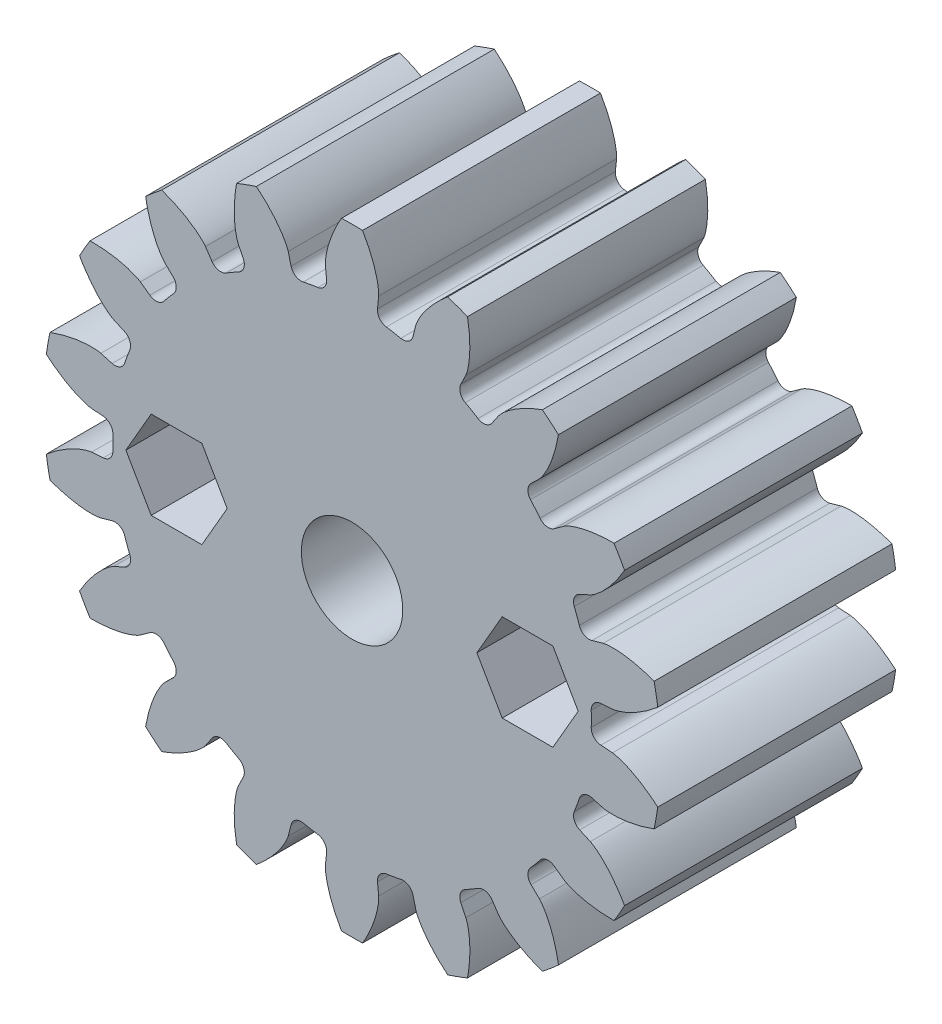
SolidWorks part; units mm, degrees
ref_plane "Front Plane" through (0, 0, 0) normal (0, 0, 1) x (1, 0, 0)
ref_plane "Top Plane" through (0, 0, 0) normal (0, 1, 0) x (1, 0, 0)
ref_plane "Right Plane" through (0, 0, 0) normal (1, 0, 0) x (0, 0, -1)
sketch "Sketch1" plane through (0, 0, 0) normal (0, 0, 1) x (1, 0, 0)
  line L0 (0, 0) -> (0, 9.525) construction
  line L1 (-3.0613, 10.6392) -> (3.0613, 8.4108) construction
  circle A0 centre (0, 0) radius 8.2021 construction
  circle A1 centre (0, 0) radius 10.5833 construction
  circle A2 centre (0, 0) radius 9.525 construction
  circle A3 centre (0, 0) radius 8.9506 construction
  circle A4 centre (0, 0) radius 2.3813 construction
  circle A5 centre (0, 0) radius 6.858 construction
  point P8 (304.8, 0)
  point P13 (228.6, 0)
  dimension "OD | Outside Diameter" = 21.1667
  dimension "Root Diameter" = 16.4042
  dimension "Gear Pitch Diameter" = 19.05
  dimension "Base Diameter" = 17.9011
  dimension "For Shaft Diameter" = 4.7625
  dimension "Hub Diameter" = 13.716
  dimension "Pressure Angle" = 20
  dimension "Number of Teeth" = 457.2
  dimension "Gear Pitch | Diametral Pitch" = 609.6
sketch "Sketch2" plane through (0, 0, 0) normal (1, 0, 0) x (0, 0, -1)
  line L0 (-6.35, 0) -> (6.35, 0) construction
  line L1 (-6.35, 10.5833) -> (6.35, 10.5833) construction
  point P2 (0, 10.5833)
  point P4 (0, 0)
  point P6 (0, 10.5833)
  dimension "Overall Width" = 12.7
  dimension "Hub Width" = 6.35
  dimension "Face Width" = 6.35
sketch "Sketch3" plane through (0, 0, 0) normal (0, 0, 1) x (1, 0, 0)
  circle A0 centre (0, 0) radius 10.5833
  circle A1 centre (0, 0) radius 10.5833 construction
extrude "Boss-Extrude1" add sketch "Sketch3" against normal blind 10.16
sketch "Sketch4" plane through (0, 0, 0) normal (0, 0, 1) x (1, 0, 0)
  line L0 (0, 0) -> (8.1806, 0.593) construction
  line L2 (0, 0) -> (8.1806, -0.593) construction
  line L4 (8.1806, 0.593) -> (8.9271, 0.6471)
  line L5 (8.9271, -0.6471) -> (8.1806, -0.593)
  arc A0 (8.1806, 0.593) -> (8.1806, -0.593) centre (0, 0) cw
  arc A3 (10.4791, 1.4815) -> (10.4791, -1.4815) centre (0, 0) cw
  circle A4 centre (0, 0) radius 10.5833 construction
  spline S0 degree 4 poles (8.9271, 0.6471) (8.9298, 0.6473) (8.9371, 0.6481) (8.951, 0.6499) (8.9735, 0.6535) (9.0022, 0.659) (9.039, 0.6671) (9.0823, 0.6779) (9.1296, 0.6912) (9.1807, 0.7071) (9.2315, 0.7243) (9.2819, 0.7426) (9.3319, 0.762) (9.3922, 0.7867) (9.464, 0.8182) (9.5473, 0.8575) (9.6409, 0.905) (9.7354, 0.9567) (9.8276, 1.0102) (9.9198, 1.0673) (10.0083, 1.1246) (10.0992, 1.1871) (10.1825, 1.2464) (10.2747, 1.3161) (10.3487, 1.3734) (10.4449, 1.4524) (10.5013, 1.5001) (10.5668, 1.5571) (10.5956, 1.5831) (10.6134, 1.599) knots 0 0 0 0 0 0.005377 0.015084 0.028532 0.04661 0.064855 0.092111 0.119476 0.146842 0.174209 0.201575 0.228941 0.256307 0.307035 0.361767 0.4165 0.471232 0.525964 0.580697 0.635429 0.690161 0.744894 0.799626 0.854358 0.909091 0.954545 1 1 1 1 1 construction
  spline S1 degree 4 poles (8.9271, 0.6471) (8.9298, 0.6473) (8.9371, 0.6481) (8.951, 0.6499) (8.9735, 0.6535) (9.0022, 0.659) (9.039, 0.6671) (9.0823, 0.6779) (9.1296, 0.6912) (9.1807, 0.7071) (9.2315, 0.7243) (9.2819, 0.7426) (9.3319, 0.762) (9.3922, 0.7867) (9.464, 0.8182) (9.5473, 0.8575) (9.6409, 0.905) (9.7354, 0.9567) (9.8276, 1.0102) (9.9198, 1.0673) (10.0083, 1.1246) (10.0992, 1.1871) (10.1825, 1.2464) (10.2747, 1.3161) (10.3487, 1.3734) (10.424, 1.4353) (10.4605, 1.4658) (10.4791, 1.4815) knots 0 0 0 0 0 0.005377 0.015084 0.028532 0.04661 0.064855 0.092111 0.119476 0.146842 0.174209 0.201575 0.228941 0.256307 0.307035 0.361767 0.4165 0.471232 0.525964 0.580697 0.635429 0.690161 0.744894 0.799626 0.854358 0.909091 0.909091 0.909091 0.909091 0.909091
  spline S2 degree 4 poles (8.9271, -0.6471) (8.9298, -0.6473) (8.9371, -0.6481) (8.951, -0.6499) (8.9735, -0.6535) (9.0022, -0.659) (9.039, -0.6671) (9.0823, -0.6779) (9.1296, -0.6912) (9.1807, -0.7071) (9.2315, -0.7243) (9.2819, -0.7426) (9.3319, -0.762) (9.3922, -0.7867) (9.464, -0.8182) (9.5473, -0.8575) (9.6409, -0.905) (9.7354, -0.9567) (9.8276, -1.0102) (9.9198, -1.0673) (10.0083, -1.1246) (10.0992, -1.1871) (10.1825, -1.2464) (10.2747, -1.3161) (10.3487, -1.3734) (10.4449, -1.4524) (10.5013, -1.5001) (10.5668, -1.5571) (10.5956, -1.5831) (10.6134, -1.599) knots 0 0 0 0 0 0.005377 0.015084 0.028532 0.04661 0.064855 0.092111 0.119476 0.146842 0.174209 0.201575 0.228941 0.256307 0.307035 0.361767 0.4165 0.471232 0.525964 0.580697 0.635429 0.690161 0.744894 0.799626 0.854358 0.909091 0.954545 1 1 1 1 1 construction
  spline S3 degree 4 poles (8.9271, -0.6471) (8.9298, -0.6473) (8.9371, -0.6481) (8.951, -0.6499) (8.9735, -0.6535) (9.0022, -0.659) (9.039, -0.6671) (9.0823, -0.6779) (9.1296, -0.6912) (9.1807, -0.7071) (9.2315, -0.7243) (9.2819, -0.7426) (9.3319, -0.762) (9.3922, -0.7867) (9.464, -0.8182) (9.5473, -0.8575) (9.6409, -0.905) (9.7354, -0.9567) (9.8276, -1.0102) (9.9198, -1.0673) (10.0083, -1.1246) (10.0992, -1.1871) (10.1825, -1.2464) (10.2747, -1.3161) (10.3487, -1.3734) (10.424, -1.4353) (10.4605, -1.4658) (10.4791, -1.4815) knots 0 0 0 0 0 0.005377 0.015084 0.028532 0.04661 0.064855 0.092111 0.119476 0.146842 0.174209 0.201575 0.228941 0.256307 0.307035 0.361767 0.4165 0.471232 0.525964 0.580697 0.635429 0.690161 0.744894 0.799626 0.854358 0.909091 0.909091 0.909091 0.909091 0.909091
  dimension "D1" = 16.4042
extrude "Cut-Extrude1" cut sketch "Sketch4" against normal through all both and the other way through all
fillet "Fillet1" radius 0.3551 2 edges at (8.1806, -0.593, -5.08) (8.1806, 0.593, -5.08)
pattern_circular "CirPattern1" count 18 over 360 about axis through (0, 0, 6.35) along (0, 0, -1) of "Cut-Extrude1", "Fillet1"
scale "Scale1" scale about centroid uniform scaling yes scale factor 1.9
sketch "Sketch6" plane through (0, 0, 4.572) normal (0, 0, 1) x (1, 0, 0)
  circle A0 centre (0, 0) radius 3.302
  dimension "D1" = 6.604
extrude "Cut-Extrude2" cut sketch "Sketch6" against normal blind 10.16
sketch "Sketch7" plane through (0, 0, -14.732) normal (0, 0, -1) x (-1, 0, 0)
  circle A0 centre (0, 0) radius 9.525
  dimension "D1" = 19.05
sketch "Sketch12" plane through (0, 0, -14.732) normal (0, 0, -1) x (-1, 0, 0)
  circle A0 centre (0, 0) radius 21.4375
extrude "Cut-Extrude7" cut sketch "Sketch12" against normal blind 3.81
sketch "Sketch13" plane through (0, 0, 4.572) normal (0, 0, 1) x (1, 0, 0)
  line L0 (0, 0) -> (0, 7.3951) construction
  line L1 (-8.1304, 0) -> (-9.7802, 2.8575)
  line L2 (-9.7802, 2.8575) -> (-13.0798, 2.8575)
  line L3 (-13.0798, 2.8575) -> (-14.7296, 0)
  line L4 (-14.7296, 0) -> (-13.0798, -2.8575)
  line L5 (-13.0798, -2.8575) -> (-9.7802, -2.8575)
  line L6 (-9.7802, -2.8575) -> (-8.1304, 0)
  line L7 (14.7296, 0) -> (13.0798, 2.8575)
  line L8 (13.0798, 2.8575) -> (9.7802, 2.8575)
  line L9 (9.7802, 2.8575) -> (8.1304, 0)
  line L10 (8.1304, 0) -> (9.7802, -2.8575)
  line L11 (9.7802, -2.8575) -> (13.0798, -2.8575)
  line L12 (13.0798, -2.8575) -> (14.7296, 0)
  circle A0 centre (-11.43, 0) radius 2.8575 construction
  circle A1 centre (11.43, 0) radius 2.8575 construction
  dimension "D1" = 5.715
  dimension "D2" = 5.715
  dimension "D3" = 22.86
  dimension "D4" = 11.43
extrude "Cut-Extrude8" cut sketch "Sketch13" against normal blind 11.43
sketch "Sketch14" plane through (0, 0, 4.572) normal (0, 0, 1) x (1, 0, 0)
  line L0 (0, 0) -> (0, 6.836) construction
  circle A0 centre (-11.43, 0) radius 1.651
  circle A1 centre (11.43, 0) radius 1.651
  dimension "D1" = 3.302
  dimension "D2" = 3.302
  dimension "D3" = 22.86
  dimension "D4" = 11.43
extrude "Cut-Extrude9" cut sketch "Sketch14" against normal through all
equation "\"Root Diameter@Sketch1\"=\"Root Diameter\""
equation "\"OD | Outside Diameter@Sketch1\"=\"Outside Diameter\""
equation "\"D1@CirPattern1\"=\"Number of Teeth\""
equation "\"Diametral Pitch\"= 24"
equation "\"Number of Teeth\"= 18"
equation "\"Pressure Angle\"=20"
equation "\"Pitch Diameter\"= \"Number of Teeth\" / \"Diametral Pitch\""
equation "\"Base Diameter\"= \"Pitch Diameter\" * cos ( \"Pressure Angle\" )"
equation "\"Outside Diameter\"= ( \"Number of Teeth\" + 2 ) / \"Diametral Pitch\""
equation "\"Dedendum\"= 1.25 / \"Diametral Pitch\""
equation "\"Root Diameter\"= \"Pitch Diameter\" - ( 2 * \"Dedendum\" )"
equation "\"Pitch Angle\"= 360deg / \"Number of Teeth\""
equation "\"Alpha\"= sqr ( \"Pitch Diameter\" ^ 2 - \"Base Diameter\" ^ 2 ) / \"Base Diameter\" * 180 / PI - \"Pressure Angle\""
equation "\"Beta\"= ( \"Pitch Angle\" / 4 - \"Alpha\" )"
equation "\"Phi\"= sqr ( ( \"Outside Diameter\" / 2 ) ^ 2 - ( \"Base Diameter\" / 2 ) ^ 2 ) / ( \"Base Diameter\" / 2 )"
equation "\"Addendum\"= 1 / \"Diametral Pitch\""
equation "\"WorkingDepth\"= 2 / \"Diametral Pitch\""
equation "\"WholeDepth\"= 2.25 / \"Diametral Pitch\""
equation "\"Clearance\"= 0.25 / \"Diametral Pitch\""
equation "\"ToothThickness\"= ( pi * 2 ) / \"Diametral Pitch\""
equation "\"CircularPitch\"= pi / \"Diametral Pitch\""
equation "\"Number of Teeth@Sketch1\"=\"Number of Teeth\""
equation "\"Gear Pitch | Diametral Pitch@Sketch1\"=\"Diametral Pitch\""
equation "\"Pressure Angle@Sketch1\"=\"Pressure Angle\""
equation "\"Gear Pitch Diameter@Sketch1\"=\"Pitch Diameter\""
equation "\"Base Diameter@Sketch1\"=\"Base Diameter\""
equation "\"Fillet\"= \"Clearance\" * cos ( \"Pressure Angle\" ) * tan ( ( 90 + \"Pressure Angle\" ) / 2 )"
equation "\"D1@Fillet1\"=\"Fillet\""
equation "\"D1@Sketch4\"=if( \"Base Diameter\">\"Root Diameter\",\"Root Diameter\",\"Base Diameter\"-.00001)"
equation "\"D1@Fillet2\"=\"Fillet\""
